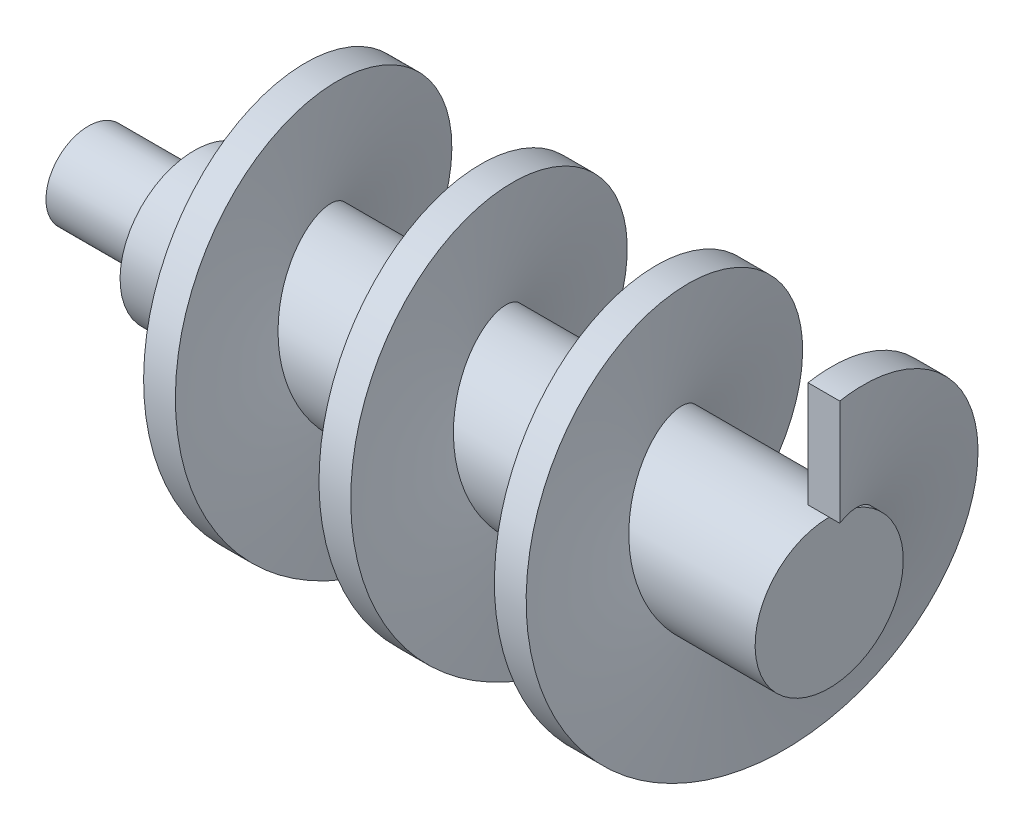
SolidWorks part; units mm, degrees
ref_plane "Alzado" through (0, 0, 0) normal (0, 0, 1) x (1, 0, 0)
ref_plane "Planta" through (0, 0, 0) normal (0, 1, 0) x (1, 0, 0)
ref_plane "Vista lateral" through (0, 0, 0) normal (1, 0, 0) x (0, 0, -1)
sketch "Croquis1" plane through (0, 0, 0) normal (0, 0, 1) x (1, 0, 0)
  line L0 (53.8688, 0) -> (-53.8688, 0) construction
  line L1 (-25, 7) -> (35, 7)
  line L2 (-25, 7) -> (-25, 4)
  line L3 (-25, 4) -> (-35, 4)
  line L4 (-35, 4) -> (-35, 0)
  line L5 (-35, 0) -> (35, 0)
  line L6 (35, 0) -> (35, 7)
  line L7 (-81.7492, 0) -> (106.9495, 0) construction
  point P3 (0, 0)
  point P5 (0, 0)
  dimension "D1" = 7
  dimension "D2" = 10
  dimension "D3" = 4
  dimension "D4" = 60
revolve "Revolución1" add sketch "Croquis1" angle 360 about L7
sketch "Croquis2" plane through (-25, 0, 0) normal (-1, 0, 0) x (0, 0, 1)
  circle A0 centre (0, 0) radius 7
  circle A1 centre (0, 0) radius 7 construction
curve "Hélice/Espiral1" pitch 16.5714 height 58 radius 7 centre (-25, 0, 0) axis (1, 0, 0) start towards (0, -1, 0)
sketch "Croquis3" plane through (0, 0, 0) normal (0, 0, 1) x (1, 0, 0)
  line L1 (-25, -7) -> (-22, -7)
  line L2 (-25, -7) -> (-25, -17)
  line L3 (-25, -17) -> (-22, -17)
  line L4 (-22, -7) -> (-22, -17)
  dimension "D1" = 10
  dimension "D2" = 3
sweep "Barrer1" add profiles "Croquis3" path "Hélice/Espiral1"
